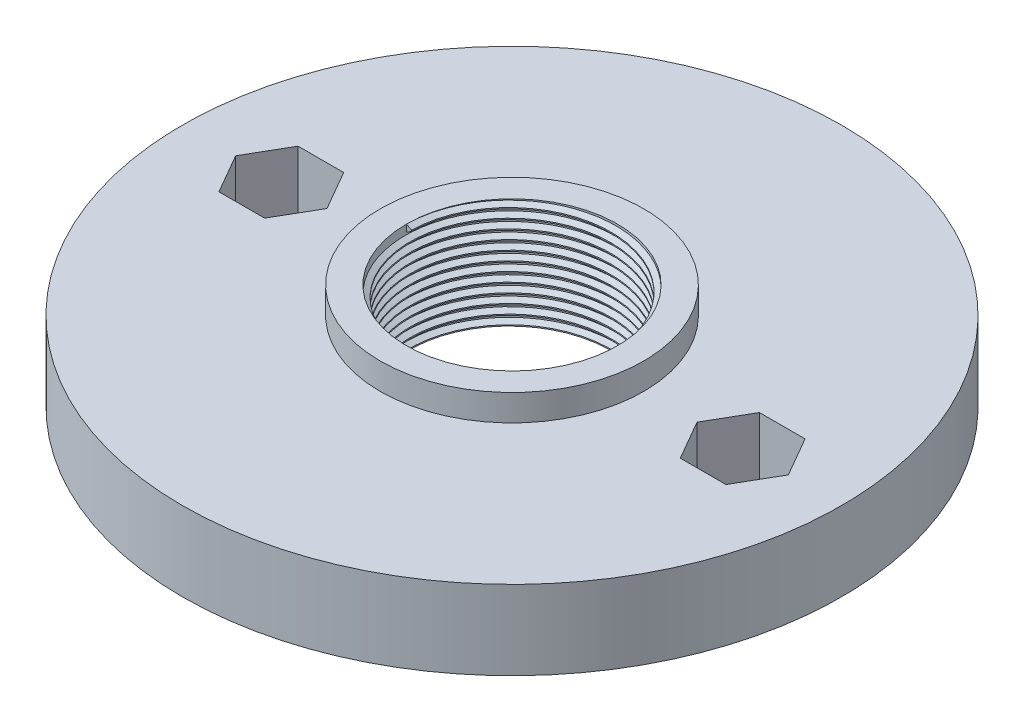
SolidWorks part; units mm, degrees
ref_plane "Front Plane" through (0, 0, 0) normal (0, 0, 1) x (1, 0, 0)
ref_plane "Top Plane" through (0, 0, 0) normal (0, 1, 0) x (1, 0, 0)
ref_plane "Right Plane" through (0, 0, 0) normal (1, 0, 0) x (0, 0, -1)
sketch "Sketch1" plane through (0, 0, 0) normal (0, 1, 0) x (1, 0, 0)
  circle A0 centre (0, 0) radius 12.5
  dimension "D1" = 25
extrude "Boss-Extrude2" add sketch "Sketch1" along normal blind 3
sketch "Sketch3" plane through (0, 3, 0) normal (0, 1, 0) x (1, 0, 0)
  circle A0 centre (0, 0) radius 5
extrude "Boss-Extrude3" add sketch "Sketch3" along normal blind 1
sketch "Sketch4" plane through (0, 4, 0) normal (0, 1, 0) x (1, 0, 0)
  circle A0 centre (0, 0) radius 4
extrude "Cut-Extrude1" cut sketch "Sketch4" against normal through all
thread "Thread1" pitch 0.35 method extrude profile "Thread Profile1" start angle 0, offset 0, length 0, pitch 0.35, diameter 8
ref_plane "Plane1" through (-4, 4, 0) normal (0, 0, -1) x (1, 0, 0)
sketch "Thread Profile1" plane through (-4, 4, 0) normal (0, 0, -1) x (1, 0, 0)
  line L0 (0, 0) -> (0, 0.35) construction
  line L1 (0, 0) -> (0.1894, 0.1094)
  line L2 (0.1894, 0.1094) -> (0.1894, 0.1531)
  line L3 (0.1894, 0.1531) -> (0, 0.2625)
  line L4 (0.1894, 0.1312) -> (0, 0.1312) construction
  line L11 (0, 0) -> (0, 0.2625)
  point P2 (0, 0)
  dimension "Pitch" = 0.35
  dimension "Profile_Angle" = 60
  dimension "Profile_Land" = 0.0437
  dimension "Profile_Height" = 0.1894
sketch "Sketch12" plane through (0, 3, 0) normal (0, 1, 0) x (1, 0, 0)
  line L1 (10.4821, 0) -> (9.616, 1.5)
  line L2 (9.616, 1.5) -> (7.884, 1.5)
  line L3 (7.884, 1.5) -> (7.0179, 0)
  line L4 (7.0179, 0) -> (7.884, -1.5)
  line L5 (7.884, -1.5) -> (9.616, -1.5)
  line L6 (9.616, -1.5) -> (10.4821, 0)
  circle A0 centre (8.75, 0) radius 1.5 construction
  dimension "D1" = 8.75
  dimension "D2" = 3
extrude "Cut-Extrude2" cut sketch "Sketch12" against normal through all
mirror "Mirror1" about plane through (0, 0, 0) normal (1, 0, 0) of "Cut-Extrude2"
